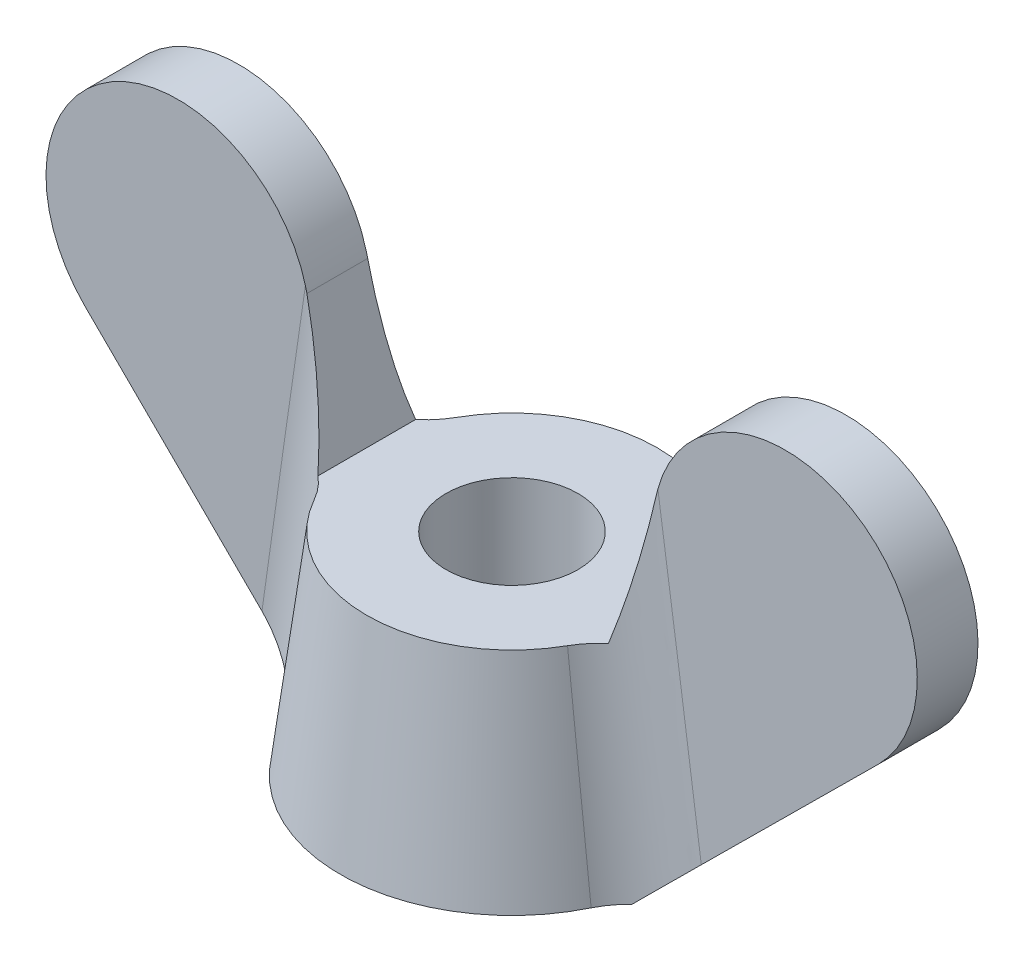
SolidWorks part; units mm, degrees
note: '?' marks a value the reader was unsure of. The reader was unsure of these and kept them because the rebuilt part matched: shared geometry of "Sketch1<3>".
material "AISI 1020"
ref_plane "XY (Front)" through (0, 0, 0) normal (0, 0, 1) x (1, 0, 0)
ref_plane "XZ (Top)" through (0, 0, 0) normal (0, 1, 0) x (1, 0, 0)
ref_plane "YZ (Right)" through (0, 0, 0) normal (1, 0, 0) x (0, 0, -1)
ref_axis "X" through (-11, 0, 0) along (1, 0, 0)?
ref_axis "Y" through (0, 27.825, 0) along (0, -1, 0)?
ref_axis "Z" through (0, 0, -4.4) along (0, 0, 1)?
sketch "Sketch1" plane through (0, 0, 0) normal (0, 0, 1) x (1, 0, 0)
  line L0 (0, 0) -> (0, 8)
  line L2 (-6.5, 0) -> (6.5, 0)
  line L3 (6.5, 0) -> (5.5, 8)
  line L4 (5.5, 8) -> (-5.5, 8)
  line L5 (0, 0) -> (0, -12.7512) construction
  line L6 (5.5, 8) -> (6.6169, 13.0747)
  line L7 (15.0207, 8.4497) -> (6.5, 0)
  line L8 (-5.5, 8) -> (-6.6169, 13.0747)
  line L9 (-15.0207, 8.4497) -> (-6.5, 0)
  line L10 (-6.5, 0) -> (-5.5, 8)
  arc A0 (6.6169, 13.0747) -> (15.0207, 8.4497) centre (11.5, 12) cw
  arc A1 (-6.6169, 13.0747) -> (-15.0207, 8.4497) centre (-11.5, 12) ccw
  dimension "r" = 5
  dimension "db" = 13
  dimension "da" = 11
  dimension "m" = 8
  dimension "e" = 33
  dimension "h" = 17
extrude "Boss-Extrude1" add sketch "Sketch1" along normal mid plane 2.3
revolve "Revolve1" add sketch "Sketch1<3>" angle 360 about L5
sketch "Sketch1<3>" plane through (0, 0, 0) normal (0, 0, 1) x (1, 0, 0) same geometry as "Sketch1"
fillet "Fillet1" radius 3 4 edges
hole_wizard "M6 Tapped Hole1" positions "Sketch3" profile "Sketch2" tap size "M6" standard "DIN" end condition up to next
sketch "Sketch3" plane through (0, 0, 0) normal (0, -1, 0) x (-1, 0, 0)
  point P0 (0, 0)
sketch "Sketch2" plane through (0, 0, 0) normal (1, 0, 0) x (0, 0, -1)
  line L0 (0, 0) -> (0, 8)
  line L1 (0, 8) -> (2.5, 8)
  line L2 (2.5, 8) -> (2.5, 0)
  line L5 (2.5, 0) -> (0, 0)
  line L11 (0, -6.35) -> (0, 107.95) construction
  dimension "Thru Tap Drill Dia." = 5
  dimension "Thru Tap Drill Depth" = 8
cosmetic thread "Hole Thread1" parameters "M"=6
